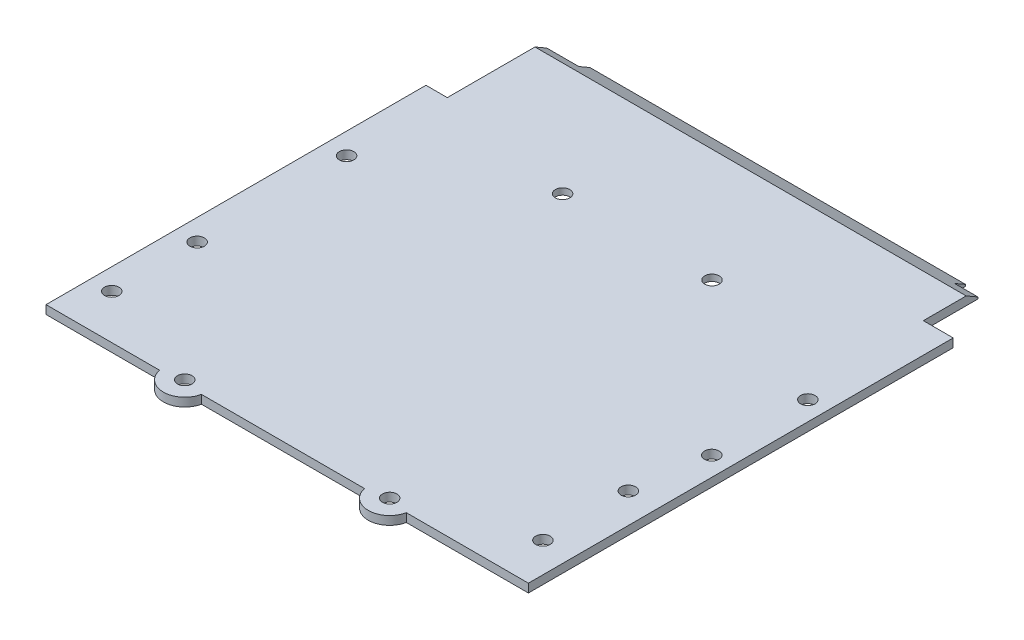
SolidWorks part; units mm, degrees
ref_plane "前视基准面" through (0, 0, 0) normal (0, 0, 1) x (1, 0, 0)
ref_plane "上视基准面" through (0, 0, 0) normal (0, 1, 0) x (1, 0, 0)
ref_plane "右视基准面" through (0, 0, 0) normal (1, 0, 0) x (0, 0, -1)
other "Configuration Table"
sketch "草图1" plane through (0, 0, 0) normal (0, 1, 0) x (1, 0, 0)
  line L1 (0, 0) -> (113, 0)
  line L2 (0, 0) -> (0, 113)
  line L3 (0, 113) -> (113, 113)
  line L4 (113, 0) -> (113, 113)
  dimension "D1" = 113
extrude "凸台-拉伸1" add sketch "草图1" along normal blind 3
sketch "草图2" plane through (0, 3, 0) normal (0, 1, 0) x (1, 0, 0)
  line L0 (108.5, 113) -> (108.5, 0) construction
  line L1 (113, 113) -> (0, 113) construction
  line L2 (0, 0) -> (113, 0) construction
  line L3 (113, 0) -> (113, 113) construction
  line L4 (106, 30.4) -> (106, 0) construction
  circle A0 centre (108.5, 69.95) radius 1.7
  circle A1 centre (108.5, 47.45) radius 1.7
  circle A2 centre (106, 30.4) radius 1.7
  circle A3 centre (106, 10.4) radius 1.7
  dimension "D2" = 47.45
  dimension "D3" = 22.5
  dimension "D4" = 3.4
  dimension "D6" = 10.4
  dimension "D7" = 20
  dimension "D1" = 4.5
  dimension "D5" = 7
extrude "切除-拉伸1" cut sketch "草图2" against normal up to next
sketch "草图3" plane through (0, 0, 0) normal (0, 1, 0) x (1, 0, 0)
  line L0 (113, 113) -> (0, 113) construction
  line L1 (10.5, 113) -> (100.5, 113)
  line L2 (10.5, 113) -> (10.5, 8)
  line L3 (10.5, 8) -> (100.5, 8)
  line L4 (100.5, 113) -> (100.5, 8)
  line L5 (113, 0) -> (113, 113) construction
  line L6 (0, 113) -> (0, 0) construction
  line L7 (0, 0) -> (113, 0) construction
  dimension "D1" = 12.5
  dimension "D2" = 10.5
  dimension "D3" = 8
extrude "凸台-拉伸2" add sketch "草图3" against normal blind 1.5
sketch "草图5" plane through (0, 0, 0) normal (0, -1, 0) x (1, 0, 0)
  line L0 (0, -1) -> (113, -1) construction
  line L1 (0, -113) -> (0, 0) construction
  line L2 (113, 0) -> (113, -113) construction
  line L3 (0, 0) -> (113, 0) construction
  circle A0 centre (79.5, -1) radius 5
  circle A1 centre (31.5, -1) radius 5
  dimension "D1" = 33.5
  dimension "D2" = 48
  dimension "D3" = 10
  dimension "D4" = 1
extrude "凸台-拉伸3" add sketch "草图5" against normal up to surface (3 mm away) up to face at (108.5, 3, -68.25)
sketch "草图6" plane through (0, 0, 0) normal (0, -1, 0) x (1, 0, 0)
  circle A0 centre (31.5, -1) radius 1.7
  circle A1 centre (79.5, -1) radius 1.7
  dimension "D1" = 3.4
extrude "切除-拉伸2" cut sketch "草图6" against normal up to next
sketch "草图7" plane through (0, 0, 0) normal (0, -1, 0) x (1, 0, 0)
  line L0 (5, 0) -> (5, -113) construction
  line L1 (0, 0) -> (26.601, 0) construction
  line L2 (10.5, -113) -> (0, -113) construction
  line L3 (0, -113) -> (0, 0) construction
  circle A0 centre (5, -10.4) radius 1.7
  circle A1 centre (5, -30.4) radius 1.7
  circle A2 centre (5, -65.4) radius 1.7
  dimension "D1" = 10.4
  dimension "D3" = 20
  dimension "D4" = 35
  dimension "D5" = 3.4
  dimension "D2" = 5
extrude "切除-拉伸3" cut sketch "草图7" against normal up to next
sketch "草图8" plane through (0, -1.5, 0) normal (0, -1, 0) x (1, 0, 0)
  line L0 (55.5, -8) -> (55.5, -113) construction
  line L1 (10.5, -8) -> (100.5, -8) construction
  line L2 (100.5, -113) -> (10.5, -113) construction
  circle A0 centre (38, -83) radius 1.7
  circle A1 centre (73, -83) radius 1.7
  dimension "D1" = 35
  dimension "D2" = 3.4
  dimension "D3" = 30
extrude "切除-拉伸4" cut sketch "草图8" against normal up to next
sketch "草图10" plane through (100.5, 0, 0) normal (1, 0, 0) x (0, 0, -1)
  line L0 (113, 0) -> (115.5981, -1.5)
  line L1 (115.5981, -1.5) -> (113, -1.5)
  line L2 (113, -1.5) -> (113, 0)
  dimension "D1" = 30
extrude "凸台-拉伸5" add sketch "草图10" against normal up to surface (90 mm away) up to face at (10.5, -0.75, -60.5)
sketch "草图11" plane through (0, -1.5, 0) normal (0, 1, 0) x (1, 0, 0)
  line L0 (33, 83) -> (33, 53)
  line L2 (43, 53) -> (43, 83)
  line L3 (68, 83) -> (68, 53)
  line L5 (78, 53) -> (78, 83)
  arc A0 (43, 83) -> (33, 83) centre (38, 83) ccw
  arc A1 (78, 83) -> (68, 83) centre (73, 83) ccw
  arc A2 (33, 53) -> (43, 53) centre (38, 53) ccw
  arc A3 (68, 53) -> (78, 53) centre (73, 53) ccw
  dimension "D1" = 10
  dimension "D2" = 30
extrude "切除-拉伸5" cut sketch "草图11" along normal blind 2
sketch "草图13" plane through (0, 0, 0) normal (0, -1, 0) x (1, 0, 0)
  line L0 (0, -113) -> (0, 0) construction
  line L1 (5, -89) -> (3, -89)
  line L2 (5, -89) -> (5, -77)
  line L3 (5, -77) -> (3, -77)
  line L4 (3, -89) -> (3, -77)
  line L7 (10.5, -113) -> (0, -113) construction
  dimension "D1" = 2
  dimension "D2" = 3
  dimension "D3" = 36
  dimension "D4" = 12
extrude "凸台-拉伸6" add sketch "草图13" along normal blind 11.5
sketch "草图14" plane through (3, 0, 0) normal (-1, 0, 0) x (0, 0, 1)
  line L1 (-113, 0) -> (0, 0) construction
  line L2 (-113, 3) -> (-113, 0) construction
  circle A0 centre (-83.5, -5) radius 1.7
  dimension "D1" = 3.4
  dimension "D2" = 29.5
  dimension "D3" = 5
extrude "切除-拉伸6" cut sketch "草图14" against normal up to next
sketch "草图15" plane through (0, 0, 0) normal (0, -1, 0) x (1, 0, 0)
  line L0 (113, -100.8756) -> (106, -113)
  line L1 (113, 0) -> (113, -113) construction
  line L2 (113, -113) -> (100.5, -113) construction
  line L3 (106, -113) -> (113, -113)
  line L4 (113, -113) -> (113, -100.8756)
  dimension "D1" = 7
  dimension "D2" = 60
extrude "切除-拉伸7" cut sketch "草图15" against normal up to next
sketch "草图16" plane through (0, 0, 0) normal (0, -1, 0) x (1, 0, 0)
  line L0 (113, -100.8756) -> (106, -113) construction
  line L1 (113, -99.5) -> (107.5, -99.5)
  line L4 (107.5, -99.5) -> (107.5, -110.4019)
  line L5 (106, -113) -> (100.5, -113) construction
  line L6 (113, 0) -> (113, -100.8756) construction
  line L7 (113, -100.8756) -> (107.5, -110.4019)
  line L8 (113, -99.5) -> (113, -100.8756)
  dimension "D1" = 13.5
  dimension "D2" = 5.5
extrude "凸台-拉伸7" add sketch "草图16" along normal blind 8.5
sketch "草图17" plane through (3, 0, 0) normal (-1, 0, 0) x (0, 0, 1)
  line L0 (-113, 0) -> (0, 0) construction
  line L1 (-77, -11.5) -> (-79, -11.5)
  line L2 (-77, -11.5) -> (-77, 0)
  line L3 (-77, 0) -> (-79, 0)
  line L4 (-79, -11.5) -> (-79, 0)
  dimension "D1" = 2
extrude "凸台-拉伸8" add sketch "草图17" along normal up to surface (3 mm away) up to face at (0, 1.5, -56.5)
fillet "圆角1" radius 1 1 edges at (3, -5.75, -79)
sketch "草图19" plane through (0, 0, 0) normal (-1, 0, 0) x (0, 0, 1)
  line L0 (-113, 0) -> (-107.8038, 3)
  line L1 (-113, 3) -> (0, 3) construction
  line L2 (-107.8038, 3) -> (-113, 3)
  line L3 (-113, 3) -> (-113, 0)
  dimension "D1" = 60
extrude "切除-拉伸8" cut sketch "草图19" against normal through all
sketch "草图20" plane through (0, 3, 0) normal (0, 1, 0) x (1, 0, 0)
  line L1 (113, 100.8756) -> (0, 100.8756)
  line L2 (113, 100.8756) -> (113, 113)
  line L3 (113, 113) -> (0, 113)
  line L4 (0, 100.8756) -> (0, 113)
extrude "切除-拉伸9" cut sketch "草图20" against normal blind 1
chamfer "倒角1" distance 1 angle 45 1 edges at (56.5, 2, -100.8756)
sketch "草图21" plane through (0, -8.5, 0) normal (0, -1, 0) x (1, 0, 0)
  line L1 (113, -99.5) -> (106, -99.5)
  line L2 (113, -99.5) -> (113, -113)
  line L3 (113, -113) -> (106, -113)
  line L4 (106, -99.5) -> (106, -113)
extrude "切除-拉伸10" cut sketch "草图21" against normal through all
sketch "草图22" plane through (0, 0, 0) normal (0, -1, 0) x (1, 0, 0)
  line L1 (5, -89) -> (0, -89)
  line L2 (5, -89) -> (5, -113)
  line L3 (5, -113) -> (0, -113)
  line L4 (0, -89) -> (0, -113)
extrude "切除-拉伸11" cut sketch "草图22" against normal through all
sketch "草图23" plane through (0, -1.5, 0) normal (0, -1, 0) x (1, 0, 0)
  line L0 (3, -89) -> (5, -89) construction
  line L1 (10.5, -115.5981) -> (12.5, -115.5981)
  line L2 (10.5, -115.5981) -> (10.5, -97)
  line L3 (10.5, -97) -> (12.5, -97)
  line L4 (12.5, -115.5981) -> (12.5, -97)
  dimension "D1" = 8
  dimension "D2" = 2
extrude "切除-拉伸12" cut sketch "草图23" against normal up to surface (1.5 mm away) up to face at (52.7647, 0, -53.0588)
chamfer "倒角2" distance 2 angle 45 1 edges at (10.5, -0.75, -97)
sketch "草图24" plane through (100.5, 0, 0) normal (1, 0, 0) x (0, 0, -1)
  line L0 (115.5981, -1.5) -> (113, 0) construction
  line L1 (115.5981, -1.5) -> (114.9053, -1.5)
  line L2 (115.5981, -1.5) -> (115.5981, -1.1)
  line L3 (115.5981, -1.1) -> (114.9053, -1.1)
  line L4 (114.9053, -1.5) -> (114.9053, -1.1)
  dimension "D1" = 0.4
extrude "切除-拉伸13" cut sketch "草图24" against normal up to surface (95.5 mm away) up to face at (5, 1.6667, -100.5479)
sketch "草图25" plane through (106, 0, 0) normal (1, 0, 0) x (0, 0, -1)
  line L0 (113, 0) -> (109.5359, 2) construction
  line L1 (113, 0) -> (112.3072, 0)
  line L2 (113, 0) -> (113, 0.4)
  line L3 (113, 0.4) -> (112.3072, 0.4)
  line L4 (112.3072, 0) -> (112.3072, 0.4)
  dimension "D1" = 0.4
extrude "切除-拉伸14" cut sketch "草图25" against normal up to surface (5.5 mm away) up to face at (100.5, -0.82, -71.7621)
sketch "草图26" plane through (5, 0, 0) normal (-1, 0, 0) x (0, 0, 1)
  line L0 (-109.5359, 2) -> (-113, 0) construction
  line L1 (-113, 0) -> (-112.3072, 0)
  line L2 (-113, 0) -> (-113, 0.4)
  line L3 (-113, 0.4) -> (-112.3072, 0.4)
  line L4 (-112.3072, 0) -> (-112.3072, 0.4)
  dimension "D1" = 0.4
extrude "切除-拉伸15" cut sketch "草图26" against normal up to surface (7.5 mm away) up to face at (12.5, -0.82, -107.3621)
sketch "草图27" plane through (0, 2, 0) normal (0, 1, 0) x (1, 0, 0)
  line L0 (5, 101.8756) -> (106, 101.8756) construction
  line L1 (0, -4) -> (113, -4)
  line L2 (0, -4) -> (0, 101.8756)
  line L3 (0, 101.8756) -> (113, 101.8756)
  line L4 (113, -4) -> (113, 101.8756)
  line L5 (113, 0) -> (113, 99.5) construction
  line L6 (0, 89) -> (0, 0) construction
  arc A0 (26.601, 0) -> (36.399, 0) centre (31.5, 1) ccw construction
extrude "切除-拉伸16" cut sketch "草图27" along normal through all
sketch "草图29" plane through (0, 0.5, 0) normal (0, -1, 0) x (1, 0, 0)
  line L1 (33, -53) -> (43, -53)
  line L2 (33, -53) -> (33, -48)
  line L3 (33, -48) -> (43, -48)
  line L4 (43, -53) -> (43, -48)
  line L5 (78, -53) -> (68, -53)
  line L6 (78, -53) -> (78, -48)
  line L7 (78, -48) -> (68, -48)
  line L8 (68, -53) -> (68, -48)
  arc A0 (43, -53) -> (33, -53) centre (38, -53) ccw construction
  arc A1 (78, -53) -> (68, -53) centre (73, -53) ccw construction
extrude "切除-拉伸17" cut sketch "草图29" along normal through all
sketch "草图30" plane through (0, 0, -48) normal (0, 0, -1) x (-1, 0, 0)
  line L4 (-43, -1.5) -> (-33, -1.5)
  line L5 (-33, -1.5) -> (-33, 0.5)
  line L6 (-33, 0.5) -> (-43, 0.5)
  line L7 (-43, 0.5) -> (-43, -1.5)
  line L8 (-43, -1.5) -> (-33, -1.5)
  line L9 (-33, -1.5) -> (-33, 0.5)
  line L10 (-33, 0.5) -> (-43, 0.5)
  line L11 (-43, 0.5) -> (-43, -1.5)
  line L12 (-78, -1.5) -> (-68, -1.5)
  line L13 (-68, -1.5) -> (-68, 0.5)
  line L14 (-68, 0.5) -> (-78, 0.5)
  line L15 (-78, 0.5) -> (-78, -1.5)
  line L16 (-78, -1.5) -> (-68, -1.5)
  line L17 (-68, -1.5) -> (-68, 0.5)
  line L18 (-68, 0.5) -> (-78, 0.5)
  line L19 (-78, 0.5) -> (-78, -1.5)
  dimension "D1" = 0
  dimension "D2" = 0
extrude "切除-拉伸18" cut sketch "草图30" against normal offset from surface (37 mm away) 3 up to face at (55.5, -0.75, -8)
sketch "草图31" plane through (0, 0.5, 0) normal (0, -1, 0) x (1, 0, 0)
  line L0 (43, -11) -> (43, -83) construction
  line L1 (33, -11) -> (43, -11)
  line L2 (33, -11) -> (33, -38)
  line L3 (33, -38) -> (43, -38)
  line L4 (43, -11) -> (43, -38)
  line L5 (68, -83) -> (68, -11) construction
  line L6 (78, -11) -> (68, -11)
  line L7 (78, -11) -> (78, -38)
  line L8 (78, -38) -> (68, -38)
  line L9 (68, -11) -> (68, -38)
  circle A0 centre (73, -83) radius 1.7 construction
  dimension "D1" = 45
extrude "凸台-拉伸9" add sketch "草图31" along normal offset from surface (1 mm away) 1 up to face at (41.1667, -1.5, -72.9684)
sketch "草图32" plane through (0, 0, 0) normal (0, -1, 0) x (1, 0, 0)
  line L1 (5, -77) -> (0, -77)
  line L2 (5, -77) -> (5, -89)
  line L3 (5, -89) -> (0, -89)
  line L4 (0, -77) -> (0, -89)
extrude "切除-拉伸19" cut sketch "草图32" along normal up to next
